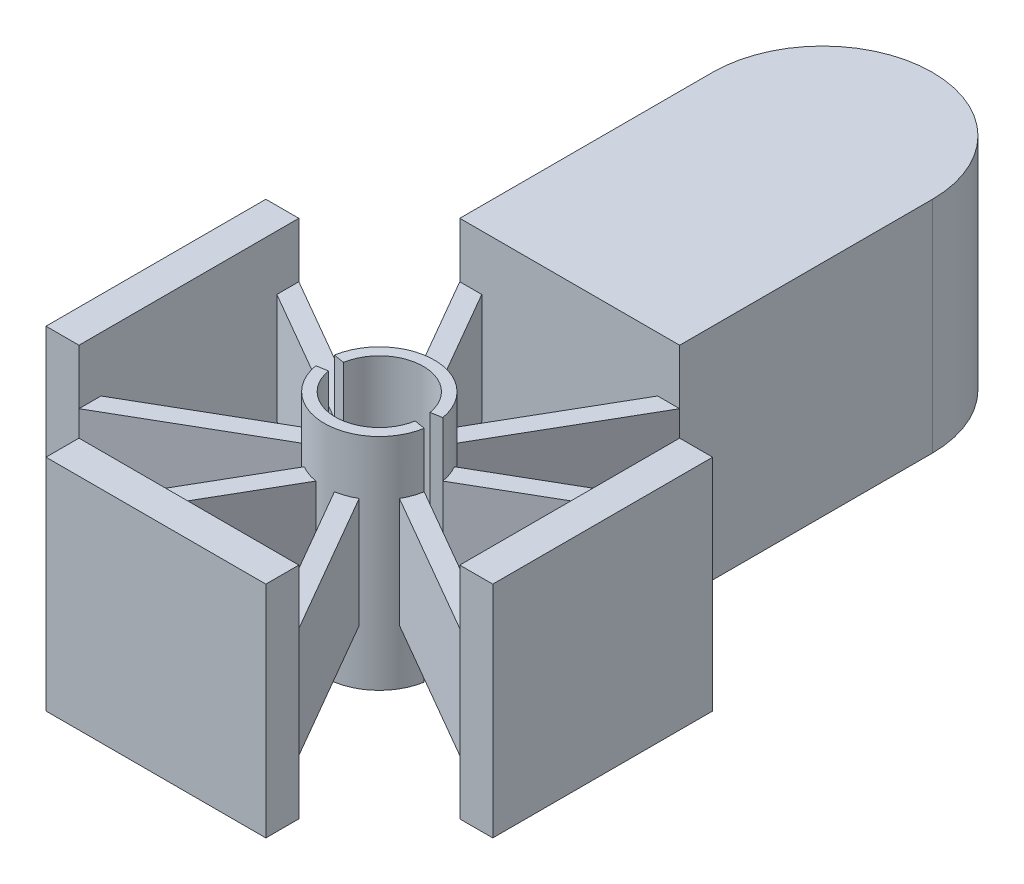
SolidWorks part; units mm, degrees
material "PET"
ref_plane "Front Plane" through (0, 0, 0) normal (0, 0, 1) x (1, 0, 0)
ref_plane "Top Plane" through (0, 0, 0) normal (0, 1, 0) x (1, 0, 0)
ref_plane "Right Plane" through (0, 0, 0) normal (1, 0, 0) x (0, 0, -1)
sketch "Sketch1" plane through (0, 0, 0) normal (0, 1, 0) x (1, 0, 0)
  line L0 (0, 0) -> (0, -10) construction
  line L1 (0, 0) -> (-1.25, -2.1651) construction
  line L2 (-1.25, -2.1651) -> (-5, -8.6603)
  line L3 (1.25, -2.1651) -> (5, -8.6603)
  line L4 (-2.1651, 1.25) -> (-8.6603, 5)
  line L5 (-2.1651, -1.25) -> (-8.6603, -5)
  line L6 (-5, -8.6603) -> (5, -8.6603)
  line L7 (5, -8.6603) -> (5, -10.1603)
  line L8 (5, -10.1603) -> (-5, -10.1603)
  line L9 (-5, -10.1603) -> (-5, -8.6603)
  line L10 (1.25, 2.1651) -> (5, 8.6603)
  line L11 (-1.25, 2.1651) -> (-5, 8.6603)
  line L12 (2.1651, -1.25) -> (8.6603, -5)
  line L13 (2.1651, 1.25) -> (8.6603, 5)
  line L14 (-8.6603, 5) -> (-8.6603, -5)
  line L15 (-10.1603, -5) -> (-10.1603, 5)
  line L16 (-10.1603, 5) -> (-8.6603, 5)
  line L17 (-8.6603, -5) -> (-10.1603, -5)
  line L18 (8.6603, 5) -> (8.6603, -5)
  line L19 (8.6603, -5) -> (10.1603, -5)
  line L20 (10.1603, -5) -> (10.1603, 5)
  line L21 (10.1603, 5) -> (8.6603, 5)
  line L22 (5, 8.6603) -> (-5, 8.6603)
  line L23 (-5, 8.6603) -> (-5, 10.1603)
  line L24 (-5, 10.1603) -> (5, 10.1603)
  line L25 (5, 10.1603) -> (5, 8.6603)
  line L26 (-8.6603, 4) -> (-2.464, 0.4226)
  line L27 (-8.6603, -4) -> (-2.464, -0.4226)
  line L28 (-4, -8.6603) -> (-0.4226, -2.464)
  line L29 (4, -8.6603) -> (0.4226, -2.464)
  line L30 (0, 0) -> (2.5, 0) construction
  line L31 (8.6603, -4) -> (2.464, -0.4226)
  line L32 (8.6603, 4) -> (2.464, 0.4226)
  line L33 (4, 8.6603) -> (0.4226, 2.464)
  line L34 (-4, 8.6603) -> (-0.4226, 2.464)
  line L35 (-1.9712, 0.3381) -> (-2.464, 0.4226)
  line L36 (1.9712, 0.3381) -> (2.464, 0.4226)
  line L37 (1.9712, -0.3381) -> (2.464, -0.4226)
  line L38 (-1.9712, -0.3381) -> (-2.464, -0.4226)
  circle A0 centre (0, 0) radius 2.5 construction
  circle A1 centre (0, 0) radius 10 construction
  arc A2 (-2.464, 0.4226) -> (2.464, 0.4226) centre (0, 0) cw
  arc A3 (-2.464, -0.4226) -> (2.464, -0.4226) centre (0, 0) ccw
  arc A4 (-1.9712, 0.3381) -> (1.9712, 0.3381) centre (0, 0) cw
  arc A5 (-1.9712, -0.3381) -> (1.9712, -0.3381) centre (0, 0) ccw
  point P5 (-1.25, -2.1651)
  point P27 (0, 0)
  dimension "D1" = 5
  dimension "D2" = 20
  dimension "D3" = 30
  dimension "D5" = 1.5
  dimension "D6" = 1
  dimension "D7" = 1
  dimension "D8" = 1
  dimension "D9" = 1
  dimension "D10" = 0.5
  dimension "D11" = 0.5
  dimension "D4" = 4
extrude "base_butterfly_blocks" add sketch "Sketch1" along normal mid plane 10 contours L9 L8 L7 L6 | L17 L14 L16 L15 | L25 L24 L23 L22 | L20 L21 L18 L19 | L35 A4 L36 A2 | A5 L38 A3 L37 region at (-1.7297, 0, 1.7297) region at (0, 0, 9.4103) region at (-9.4103, 0, 0) region at (-2.3006, 0, -0.8313) region at (9.4103, 0, 0) region at (0, 0, -9.4103)
extrude "base_butterfly_flexures" add sketch "Sketch1<4>" along normal mid plane 5 contours L26 A2 L4 L14 | L11 A2 L34 L22 | L33 A2 L10 L22 | L13 A2 L32 L18 | A3 L12 L18 L31 | A3 L29 L6 L3 | A3 L2 L6 L28 | A3 L27 L14 L5 region at (-2.6784, 0, 5.4983) region at (-5.4983, 0, 2.6784) region at (2.6784, 0, 5.4983) region at (-5.4983, 0, -2.6784) region at (5.4983, 0, 2.6784) region at (-2.6784, 0, -5.4983) region at (5.4983, 0, -2.6784) region at (2.6784, 0, -5.4983)
sketch "Sketch1<4>" plane through (0, 0, 0) normal (0, 1, 0) x (1, 0, 0) same geometry as "Sketch1"
sketch "Sketch3" plane through (0, 0, -10.1603) normal (0, 0, -1) x (-1, 0, 0)
  line L4 (-5, -5) -> (5, -5)
  line L5 (5, -5) -> (5, 5)
  line L6 (5, 5) -> (-5, 5)
  line L7 (-5, 5) -> (-5, -5)
  line L8 (-5, -5) -> (5, -5)
  line L9 (5, -5) -> (5, 5)
  line L10 (5, 5) -> (-5, 5)
  line L11 (-5, 5) -> (-5, -5)
  dimension "D1" = 0
extrude "Boss-Extrude4" add sketch "Sketch3" along normal blind 10
sketch "Sketch4" plane through (0, 5, 0) normal (0, 1, 0) x (1, 0, 0)
  line L0 (-5, 20.1603) -> (5, 20.1603) construction
  line L1 (-5, 20.1603) -> (5, 20.1603)
  arc A0 (-5, 20.1603) -> (5, 20.1603) centre (0, 20.1603) cw
  line M2 (5, 20.1603) -> (-5, 20.1603)
extrude "Boss-Extrude5" add sketch "Sketch4" against normal up to surface (10 mm away) contours A0 M2 region at (0, 5, -22.2823) up to face at (0, -5, -14.4103)
equation "\"a\"= 1mm'flexure blade width"
equation "\"D6@Sketch1\"=\"a\""
equation "\"D7@Sketch1\"=\"a\""
equation "\"D8@Sketch1\"=\"a\""
equation "\"D9@Sketch1\"=\"a\""
